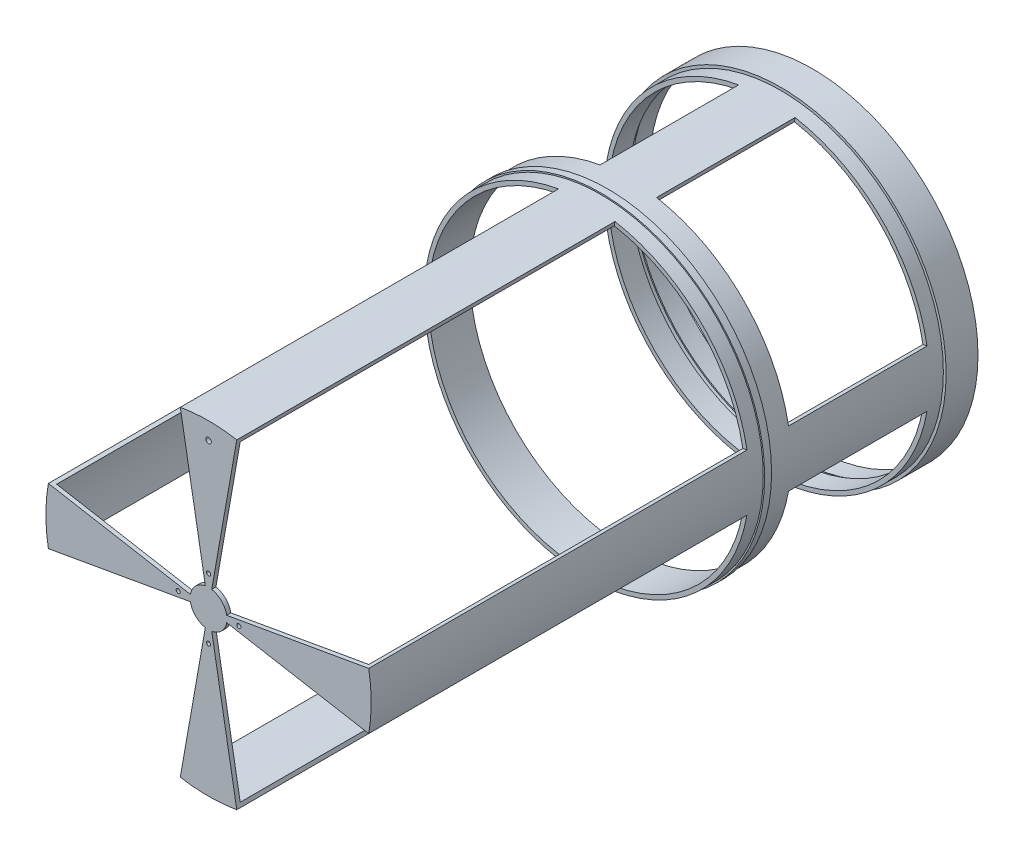
SolidWorks part; units mm, degrees
ref_plane "Front Plane" through (0, 0, 0) normal (0, 0, 1) x (1, 0, 0)
ref_plane "Top Plane" through (0, 0, 0) normal (0, 1, 0) x (1, 0, 0)
ref_plane "Right Plane" through (0, 0, 0) normal (1, 0, 0) x (0, 0, -1)
sketch "Sketch1" plane through (0, 0, 0) normal (0, 0, 1) x (1, 0, 0)
  circle A0 centre (0, 0) radius 114.4
  circle A1 centre (0, 0) radius 119.4
extrude "Extrude1" add sketch "Sketch1" against normal blind 5
sketch "Sketch2" plane through (0, 0, -5) normal (0, 0, -1) x (-1, 0, 0)
  circle A0 centre (0, 0) radius 119.4
  circle A1 centre (0, 0) radius 118.4
extrude "Extrude2" add sketch "Sketch2" along normal blind 5
sketch "Sketch3" plane through (0, 0, -10) normal (0, 0, -1) x (-1, 0, 0)
  circle A0 centre (0, 0) radius 119.4
  circle A1 centre (0, 0) radius 117.4
extrude "Extrude3" add sketch "Sketch3" along normal blind 13
sketch "Sketch4" plane through (0, 0, 0) normal (0, 0, 1) x (1, 0, 0)
  circle A0 centre (0, 0) radius 114.4
  circle A1 centre (0, 0) radius 117.4
extrude "Extrude4" add sketch "Sketch4" along normal blind 10
sketch "Sketch5" plane through (0, 0, 10) normal (0, 0, 1) x (1, 0, 0)
  line L0 (0, 0) -> (-26.3363, 149.3606) construction
  line L1 (0, 0) -> (156.0693, 27.5192) construction
  line L2 (0, 0) -> (28.315, -160.5824) construction
  line L3 (0, 0) -> (-167.0862, -29.4618) construction
  line L4 (0, 0) -> (148.5941, -26.2012) construction
  line L5 (0, 0) -> (-30.1322, -170.8882) construction
  line L6 (0, 0) -> (-160.0063, 28.2134) construction
  line L7 (0, 0) -> (24.311, 137.8747) construction
  line L8 (20.3863, 115.6164) -> (19.8654, 112.662)
  line L9 (-20.3863, 115.6164) -> (-19.8654, 112.662)
  line L10 (115.6164, 20.3863) -> (112.662, 19.8654)
  line L11 (115.6164, -20.3863) -> (112.662, -19.8654)
  line L12 (19.8654, -112.662) -> (20.3863, -115.6164)
  line L13 (-19.8654, -112.662) -> (-20.3863, -115.6164)
  line L14 (-112.662, -19.8654) -> (-115.6164, -20.3863)
  line L15 (-112.662, 19.8654) -> (-115.6164, 20.3863)
  arc A0 (112.662, 19.8654) -> (112.662, -19.8654) centre (0, 0) cw
  circle A2 centre (0, 0) radius 114.4 construction
  arc A4 (115.6164, 20.3863) -> (115.6164, -20.3863) centre (0, 0) cw
  circle A5 centre (0, 0) radius 117.4 construction
  arc A6 (19.8654, -112.662) -> (-19.8654, -112.662) centre (0, 0) cw
  arc A7 (20.3863, -115.6164) -> (-20.3863, -115.6164) centre (0, 0) cw
  arc A8 (-112.662, -19.8654) -> (-112.662, 19.8654) centre (0, 0) cw
  arc A9 (-115.6164, -20.3863) -> (-115.6164, 20.3863) centre (0, 0) cw
  circle A10 centre (0, 0) radius 117.4 construction
  arc A11 (-19.8654, 112.662) -> (19.8654, 112.662) centre (0, 0) cw
  arc A12 (-20.3863, 115.6164) -> (20.3863, 115.6164) centre (0, 0) cw
  point P0 (0, 0)
extrude "Extrude5" add sketch "Sketch5" along normal blind 100
sketch "Sketch6" plane through (0, 0, 110) normal (0, 0, 1) x (1, 0, 0)
  circle A0 centre (0, 0) radius 114.4
  circle A1 centre (0, 0) radius 117.4
  point P0 (0, 0)
extrude "Extrude7" add sketch "Sketch6" along normal blind 15
sketch "Sketch7" plane through (0, 0, 125) normal (0, 0, 1) x (1, 0, 0)
  circle A0 centre (0, 0) radius 114.4
  circle A1 centre (0, 0) radius 118.4
  point P0 (0, 0)
extrude "Extrude8" add sketch "Sketch7" along normal blind 5
sketch "Sketch8" plane through (0, 0, 130) normal (0, 0, 1) x (1, 0, 0)
  circle A0 centre (0, 0) radius 114.4
  circle A1 centre (0, 0) radius 117.4
  point P0 (0, 0)
extrude "Extrude9" add sketch "Sketch8" along normal blind 10
sketch "Sketch9" plane through (0, 0, 140) normal (0, 0, 1) x (1, 0, 0)
  line L0 (0, 0) -> (164.537, 29.0123) construction
  line L1 (0, 0) -> (-25.7683, 146.1394) construction
  line L2 (0, 0) -> (-163.4787, -28.8257) construction
  line L3 (0, 0) -> (26.4081, -149.7676) construction
  line L4 (0, 0) -> (25.7878, 146.2502) construction
  line L5 (0, 0) -> (151.073, -26.6382) construction
  line L6 (0, 0) -> (-29.2914, -166.1196) construction
  line L7 (0, 0) -> (-217.9992, 38.4391) construction
  line L8 (-20.3863, 115.6164) -> (-19.8654, 112.662)
  line L9 (20.3863, 115.6164) -> (19.8654, 112.662)
  line L10 (112.662, 19.8654) -> (115.6164, 20.3863)
  line L11 (112.662, -19.8654) -> (115.6164, -20.3863)
  line L12 (19.8654, -112.662) -> (20.3863, -115.6164)
  line L13 (-19.8654, -112.662) -> (-20.3863, -115.6164)
  line L14 (-112.662, -19.8654) -> (-115.6164, -20.3863)
  line L15 (-112.662, 19.8654) -> (-115.6164, 20.3863)
  arc A0 (112.662, -19.8654) -> (112.662, 19.8654) centre (0, 0) ccw
  arc A1 (115.6164, -20.3863) -> (115.6164, 20.3863) centre (0, 0) ccw
  circle A2 centre (0, 0) radius 117.4 construction
  arc A3 (19.8654, -112.662) -> (-19.8654, -112.662) centre (0, 0) cw
  arc A4 (20.3863, -115.6164) -> (-20.3863, -115.6164) centre (0, 0) cw
  arc A5 (-112.662, -19.8654) -> (-112.662, 19.8654) centre (0, 0) cw
  circle A6 centre (0, 0) radius 114.4 construction
  arc A7 (-115.6164, -20.3863) -> (-115.6164, 20.3863) centre (0, 0) cw
  arc A8 (-19.8654, 112.662) -> (19.8654, 112.662) centre (0, 0) cw
  arc A9 (-20.3863, 115.6164) -> (20.3863, 115.6164) centre (0, 0) cw
  point P0 (0, 0)
extrude "Extrude10" add sketch "Sketch9" along normal blind 270
sketch "Sketch10" plane through (0, 0, 410) normal (0, 0, 1) x (1, 0, 0)
  line L0 (0, 0) -> (115.6164, 20.3863) construction
  line L1 (0, 0) -> (115.6164, -20.3863) construction
  line L2 (0, 0) -> (20.3863, -115.6164) construction
  line L3 (0, 0) -> (-20.3863, -115.6164) construction
  line L4 (0, 0) -> (-115.6164, -20.3863) construction
  line L5 (0, 0) -> (-115.6164, 20.3863) construction
  line L6 (0, 0) -> (20.3863, 115.6164) construction
  line L7 (0, 0) -> (-20.3863, 115.6164) construction
  line L8 (0, 0) -> (137.0063, 0) construction
  line L9 (0, 0) -> (0, 89.4745) construction
  line L10 (0, 0) -> (-84.9341, 0) construction
  line L11 (0, 0) -> (0, -91.1649) construction
  line L12 (13.0652, 2.3038) -> (115.6164, 20.3863)
  line L13 (13.0652, -2.3038) -> (115.6164, -20.3863)
  line L14 (2.3038, -13.0652) -> (20.3863, -115.6164)
  line L15 (-20.3863, -115.6164) -> (-2.3038, -13.0652)
  line L16 (-13.0652, -2.3038) -> (-115.6164, -20.3863)
  line L17 (-115.6164, 20.3863) -> (-13.0652, 2.3038)
  line L18 (-2.3038, 13.0652) -> (-20.3863, 115.6164)
  line L19 (20.3863, 115.6164) -> (2.3038, 13.0652)
  circle A0 centre (0, 0) radius 117.4 construction
  arc A1 (-115.6164, 20.3863) -> (-115.6164, -20.3863) centre (0, 0) ccw construction
  circle A2 centre (0, 0) radius 13.2668 construction
  circle A3 centre (21.92, 0) radius 1.5
  circle A4 centre (0, -21.92) radius 1.5
  circle A5 centre (-21.92, 0) radius 1.5
  circle A6 centre (0, 21.92) radius 1.5
  arc A7 (115.6164, 20.3863) -> (115.6164, -20.3863) centre (0, 0) cw
  arc A9 (2.3038, 13.0652) -> (13.0652, 2.3038) centre (0, 0) cw
  arc A10 (13.0652, -2.3038) -> (2.3038, -13.0652) centre (0, 0) cw
  arc A11 (-2.3038, -13.0652) -> (-13.0652, -2.3038) centre (0, 0) cw
  arc A12 (-13.0652, 2.3038) -> (-2.3038, 13.0652) centre (0, 0) cw
  arc A16 (-115.6164, -20.3863) -> (-115.6164, 20.3863) centre (0, 0) cw
  arc A18 (-20.3863, 115.6164) -> (20.3863, 115.6164) centre (0, 0) cw
  arc A19 (20.3863, 115.6164) -> (-20.3863, 115.6164) centre (0, 0) ccw construction
  arc A20 (20.3863, -115.6164) -> (-20.3863, -115.6164) centre (0, 0) cw
  circle A21 centre (0, 105.0432) radius 2
  point P0 (0, 0)
  point P26 (21.92, 0)
  point P27 (0, 21.92)
  point P29 (-21.92, 0)
  point P31 (0, -21.92)
  point P50 (0, 105.0432)
  dimension "D1" = 21.92
  dimension "D2" = 21.92
  dimension "D3" = 21.92
  dimension "D4" = 21.92
extrude "Extrude11" add sketch "Sketch10" along normal blind 3
